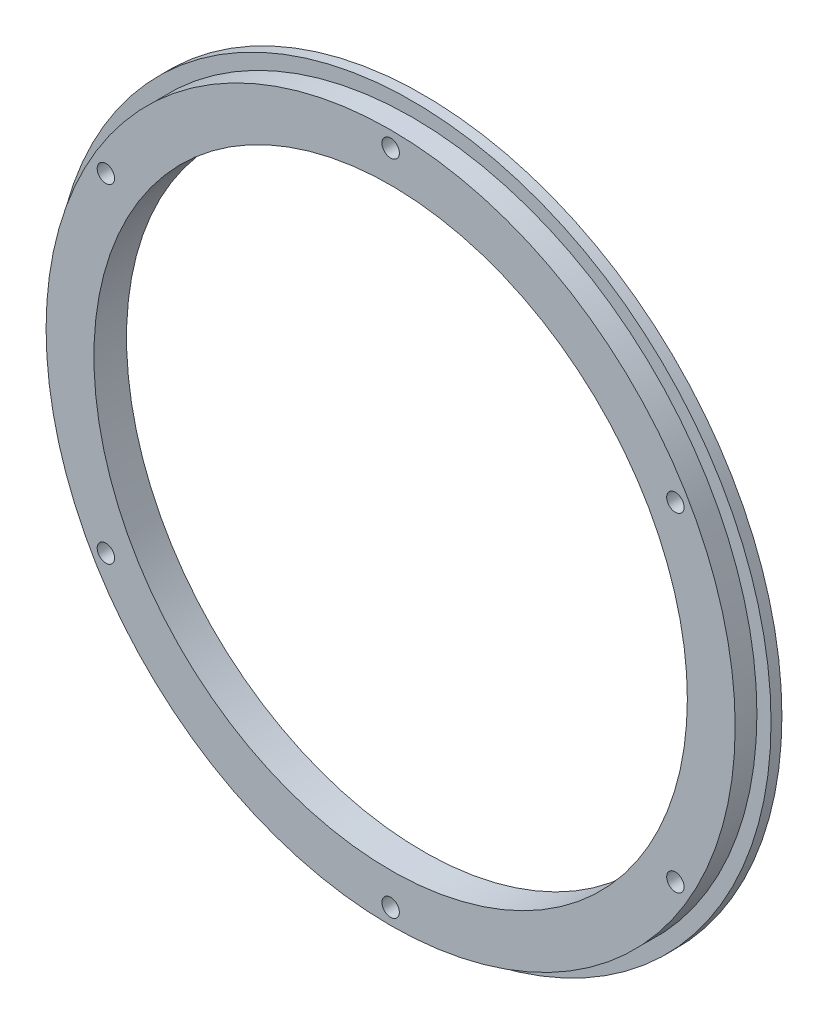
SolidWorks part; units mm, degrees
ref_plane "Front Plane" through (0, 0, 0) normal (0, 0, 1) x (1, 0, 0)
ref_plane "Top Plane" through (0, 0, 0) normal (0, 1, 0) x (1, 0, 0)
ref_plane "Right Plane" through (0, 0, 0) normal (1, 0, 0) x (0, 0, -1)
sketch "Sketch1" plane through (0, 0, 0) normal (0, 0, 1) x (1, 0, 0)
  circle A0 centre (0, 0) radius 66
extrude "Boss-Extrude1" add sketch "Sketch1" along normal blind 2
sketch "Sketch2" plane through (0, 0, 2) normal (0, 0, 1) x (1, 0, 0)
  circle A0 centre (0, 0) radius 63.4
extrude "Boss-Extrude2" add sketch "Sketch2" along normal blind 4
sketch "Sketch3" plane through (0, 0, 6) normal (0, 0, 1) x (1, 0, 0)
  circle A0 centre (0, 0) radius 54.6
extrude "Cut-Extrude1" cut sketch "Sketch3" against normal blind 10
sketch "Sketch4" plane through (0, 0, 6) normal (0, 0, 1) x (1, 0, 0)
  circle A1 centre (0, 60.5) radius 1.6
  circle A2 centre (52.3945, 30.25) radius 1.6
  circle A3 centre (52.3945, -30.25) radius 1.6
  circle A4 centre (0, -60.5) radius 1.6
  circle A5 centre (-52.3945, -30.25) radius 1.6
  circle A6 centre (-52.3945, 30.25) radius 1.6
  point P16 (0, 0)
  dimension "D1" = 6
extrude "Cut-Extrude2" cut sketch "Sketch4" against normal blind 10
